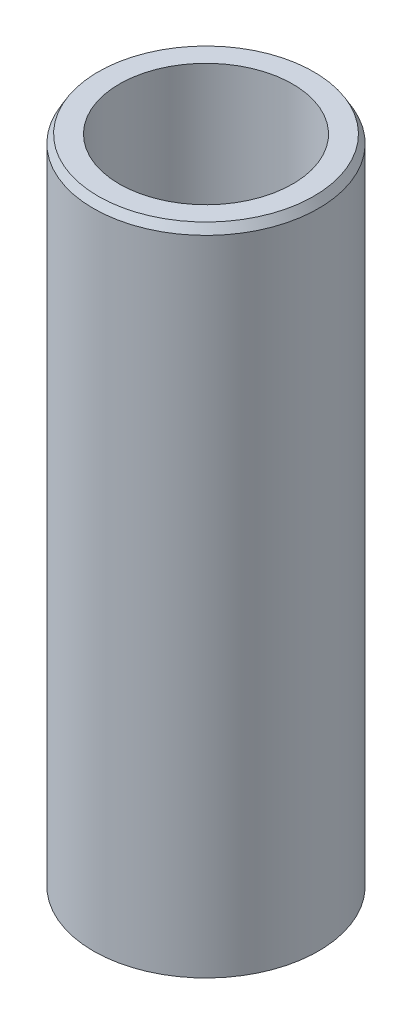
SolidWorks part; units mm, degrees
ref_plane "Front Plane" through (0, 0, 0) normal (0, 0, 1) x (1, 0, 0)
ref_plane "Top Plane" through (0, 0, 0) normal (0, 1, 0) x (1, 0, 0)
ref_plane "Right Plane" through (0, 0, 0) normal (1, 0, 0) x (0, 0, -1)
sketch "Sketch1" plane through (0, 0, 0) normal (0, 1, 0) x (1, 0, 0)
  circle A0 centre (0, 0) radius 50
  dimension "SHAFT_OD" = 100
extrude "Boss-Extrude1" add sketch "Sketch1" along normal blind 291.4583
sketch "Sketch2" plane through (0, 0, 0) normal (0, 1, 0) x (1, 0, 0)
  circle A0 centre (0, 0) radius 38.4983
  dimension "BORE_D" = 76.9967
extrude "Cut-Extrude1" cut sketch "Sketch2" along normal through all
chamfer "Chamfer1" distance 3.6572 angle 30 2 edges at (0, 291.4583, 50) (0, 0, 50) first distance on face at (0, 291.4583, 50) first distance on face at (0, 0, 38.4983)
